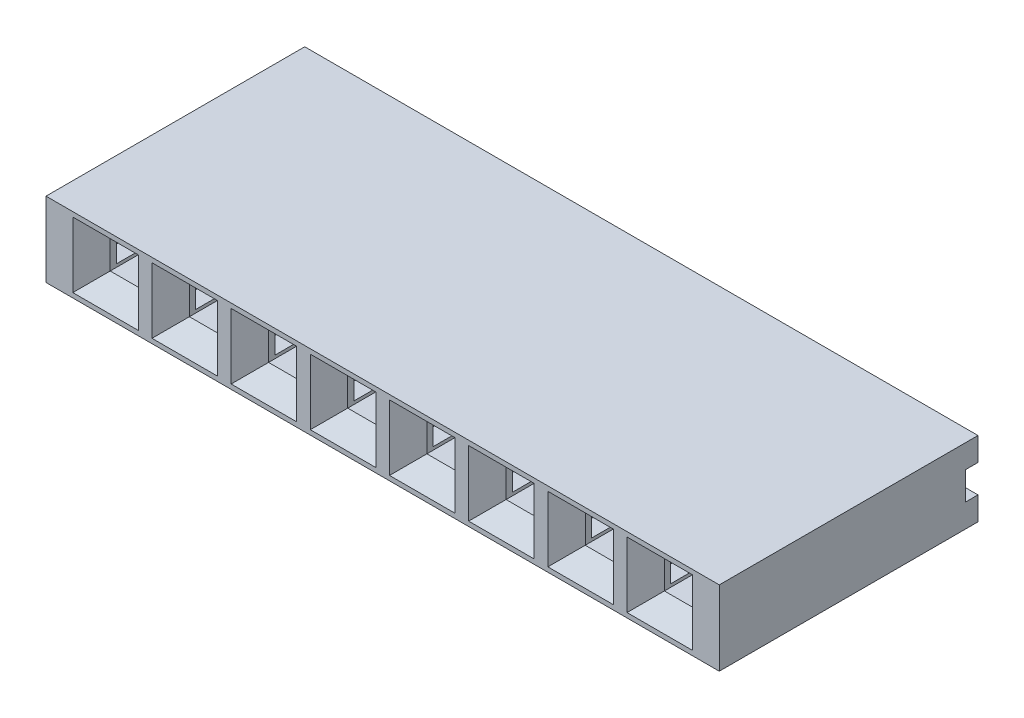
SolidWorks part; units mm, degrees
note: The reader was unsure of these and kept them because the rebuilt part matched: shared geometry of "Эскиз-БоковаяНакладка<2>".
other "Пластик"
ref_plane "Front Plane" through (0, 0, 0) normal (0, 0, 1) x (1, 0, 0)
ref_plane "Top Plane" through (0, 0, 0) normal (0, 1, 0) x (1, 0, 0)
ref_plane "Right Plane" through (0, 0, 0) normal (1, 0, 0) x (0, 0, -1)
sketch "Эскиз-ВнутреннееСечение" plane through (0, 0, 0) normal (0, 0, 1) x (1, 0, 0)
  line L0 (-1, 0.35) -> (-0.45, 0.35)
  line L1 (-1.27, -1.2) -> (1.27, -1.2)
  line L2 (-1.27, -1.2) -> (-1.27, 1.2)
  line L3 (-1.27, 1.2) -> (1.27, 1.2)
  line L4 (1.27, -1.2) -> (1.27, 1.2)
  line L5 (-1.27, -1.2) -> (1.27, 1.2) construction
  line L6 (-1.27, 1.2) -> (1.27, -1.2) construction
  line L8 (-1, -0.35) -> (-1, 0.35)
  line L9 (-0.45, 0.45) -> (0.45, 0.45)
  line L11 (0, 1.2) -> (0, -1.2) construction
  line L12 (0.45, 0.35) -> (0.45, 0.45)
  line L13 (-1.27, 0) -> (1.27, 0) construction
  line L14 (1, 0.35) -> (0.45, 0.35)
  line L15 (-0.45, 0.35) -> (-0.45, 0.45)
  line L16 (1, -0.35) -> (0.45, -0.35)
  line L17 (0.45, -0.35) -> (0.45, -0.45)
  line L18 (-0.45, -0.35) -> (-0.45, -0.45)
  line L19 (-1, -0.35) -> (-0.45, -0.35)
  line L20 (-0.45, -0.45) -> (0.45, -0.45)
  line L21 (1, -0.35) -> (1, 0.35)
  point P0 (0, 0)
  point P5 (0, 0)
  dimension "D1" = 2.4
  dimension "D2" = 2.54
  dimension "D3" = 1
  dimension "D4" = 0.35
  dimension "D5" = 0.1
  dimension "D7" = 0.55
extrude "Бобышка-ОтЦентраВверхВниз" add sketch "Эскиз-ВнутреннееСечение" against normal blind 0.4 and the other way blind 6.7 contours L8 L0 L15 L9 L12 L14 L21 L16 L17 L20 L18 L19
sketch "Эскиз-СамыйНиз" plane through (0, 0, -0.4) normal (0, 0, -1) x (-1, 0, 0)
  line L1 (1.27, 1.2) -> (1.27, -1.2) construction
  line L2 (-1.27, -1.2) -> (-1.27, 1.2) construction
  line L3 (0.45, -0.45) -> (-0.45, -0.45) construction
  line L4 (1.27, -1.2) -> (-1.27, -1.2)
  line L5 (1.27, -1.2) -> (1.27, -0.45)
  line L6 (1.27, -0.45) -> (-1.27, -0.45)
  line L7 (-1.27, -1.2) -> (-1.27, -0.45)
  line L9 (-1.27, 1.2) -> (1.27, 1.2)
  line L10 (-1.27, 1.2) -> (-1.27, 0.45)
  line L11 (-1.27, 0.45) -> (1.27, 0.45)
  line L12 (1.27, 1.2) -> (1.27, 0.45)
  line L13 (-0.45, 0.45) -> (0.45, 0.45) construction
  point P11 (0, 0)
extrude "Бобышка-СамыйНиз" add sketch "Эскиз-СамыйНиз" along normal blind 0.4
sketch "Эскиз-ВерхняяПеремычка" plane through (0, 0, 6.7) normal (0, 0, 1) x (1, 0, 0)
  line L1 (-1.27, 1.2) -> (1.27, 1.2)
  line L2 (-1.27, 1.2) -> (-1.27, -1.2)
  line L3 (-1.27, -1.2) -> (1.27, -1.2)
  line L4 (1.27, 1.2) -> (1.27, -1.2)
  line L5 (-0.45, -0.45) -> (0.45, -0.45)
  line L6 (-0.45, -0.45) -> (-0.45, 0.45)
  line L7 (-0.45, 0.45) -> (0.45, 0.45)
  line L8 (0.45, -0.45) -> (0.45, 0.45)
  line L9 (-0.45, -0.45) -> (0.45, 0.45) construction
  line L10 (-0.45, 0.45) -> (0.45, -0.45) construction
  point P4 (0, 0)
extrude "Бобышка-СамыйВерх" add sketch "Эскиз-ВерхняяПеремычка" along normal blind 0.8
chamfer "Фаска-СверхуВнутрь" distance 0.6 angle 45 4 edges at (0, -0.45, 7.5) (0.45, 0, 7.5) (0, 0.45, 7.5) (-0.45, 0, 7.5)
pattern_linear "Пластик_Массив" count 8 spacing 2.54 along (-1, 0, 0) of bodies 103
combine bodies "Соединить_Массив" operation type add bodies to combine 103 110 109 108 107 106 105 104
sketch "Эскиз-БоковаяНакладка" plane through (1.27, 0, 0) normal (1, 0, 0) x (0, 0, -1)
  line L1 (0.8, 1.2) -> (0.8, 0.45)
  line L2 (0.8, 0.45) -> (0.4, 0.45)
  line L3 (0.4, 0.45) -> (0.4, -0.45)
  line L4 (0.4, -0.45) -> (0.4, 0.45) construction
  line L5 (0.4, -0.45) -> (0.8, -0.45)
  line L6 (0.8, -0.45) -> (0.8, -1.2)
  line L7 (0.8, -1.2) -> (-7.5, -1.2)
  line L8 (-7.5, -1.2) -> (-7.5, 1.2)
  line L9 (-7.5, 1.2) -> (0.8, 1.2)
extrude "Бобышка-БоковаяНакладка1" add sketch "Эскиз-БоковаяНакладка" along normal blind 0.64 from surface at 0 starting at face at (1.27, 0, 1.375)
extrude "Бобышка-БоковаяНакладка2" add sketch "Эскиз-БоковаяНакладка<2>" against normal blind 0.64 from surface
sketch "Эскиз-БоковаяНакладка<2>" plane through (1.27, 0, 0) normal (1, 0, 0) x (0, 0, -1) same geometry as "Эскиз-БоковаяНакладка"
